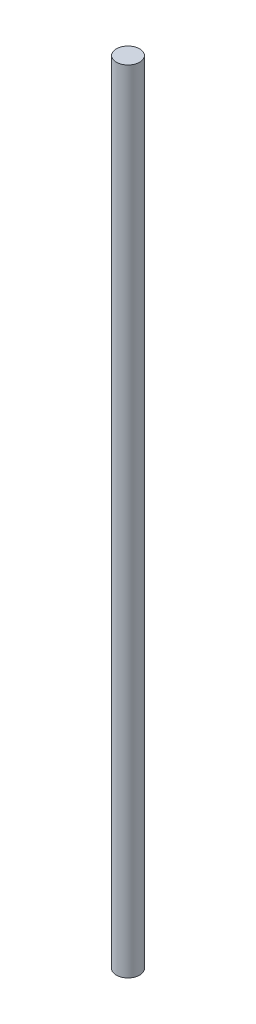
SolidWorks part; units mm, degrees
ref_plane "Front Plane" through (0, 0, 0) normal (0, 0, 1) x (1, 0, 0)
ref_plane "Top Plane" through (0, 0, 0) normal (0, 1, 0) x (1, 0, 0)
ref_plane "Right Plane" through (0, 0, 0) normal (1, 0, 0) x (0, 0, -1)
sketch "Sketch1" plane through (0, 0, 0) normal (0, 1, 0) x (1, 0, 0)
  circle A0 centre (1.3284, 0) radius 5
extrude "Boss-Extrude1" add sketch "Sketch1" along normal blind 340 contours A0
